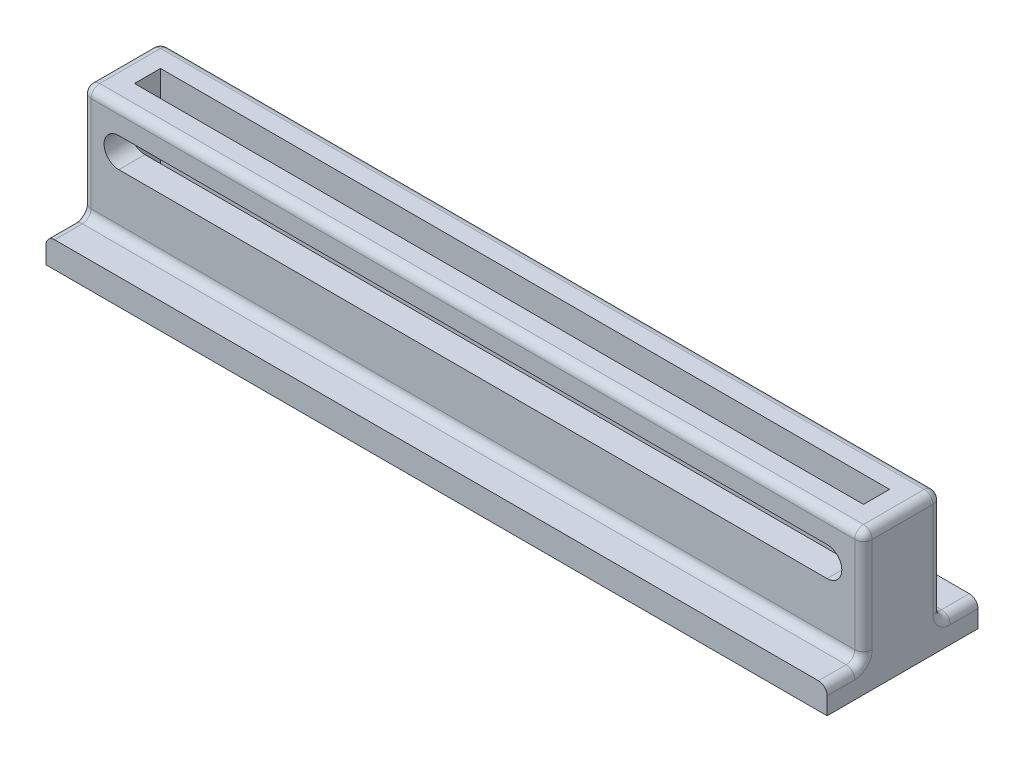
SolidWorks part; units mm, degrees
ref_plane "Front Plane" through (0, 0, 0) normal (0, 0, 1) x (1, 0, 0)
ref_plane "Top Plane" through (0, 0, 0) normal (0, 1, 0) x (1, 0, 0)
ref_plane "Right Plane" through (0, 0, 0) normal (1, 0, 0) x (0, 0, -1)
sketch "Sketch2" plane through (0, 0, 0) normal (0, 1, 0) x (1, 0, 0)
  line L1 (-45, 8.6916) -> (45, 8.6916)
  line L2 (-45, 8.6916) -> (-45, -8.6916)
  line L3 (-45, -8.6916) -> (45, -8.6916)
  line L4 (45, 8.6916) -> (45, -8.6916)
  line L5 (-45, 8.6916) -> (45, -8.6916) construction
  line L6 (-45, -8.6916) -> (45, 8.6916) construction
  point P0 (0, 0)
  dimension "D1" = 17.3831
  dimension "D2" = 90
extrude "Boss-Extrude1" add sketch "Sketch2" along normal blind 3
sketch "Sketch5" plane through (0, 3, 0) normal (0, 1, 0) x (1, 0, 0)
  line L0 (45, -8.6916) -> (45, 8.6916) construction
  line L1 (-45, 4.5) -> (45, 4.5)
  line L2 (-45, 4.5) -> (-45, -4.5)
  line L3 (-45, -4.5) -> (45, -4.5)
  line L4 (45, 4.5) -> (45, -4.5)
  line L5 (-45, 4.5) -> (45, -4.5) construction
  line L6 (-45, -4.5) -> (45, 4.5) construction
  line L7 (-42, 1.5) -> (-42, -1.5)
  line L8 (-42, -1.5) -> (42, -1.5)
  line L9 (42, 1.5) -> (42, -1.5)
  line L10 (-42, 1.5) -> (42, 1.5)
  point P0 (0, 0)
  dimension "D1" = 9
  dimension "D2" = 90
  dimension "D3" = 3
extrude "Boss-Extrude2" add sketch "Sketch5" along normal blind 13
sketch "Sketch6" plane through (0, 0, -4.5) normal (0, 0, -1) x (-1, 0, 0)
  line L0 (0, 3) -> (0, 16) construction
  line L1 (-45, 3) -> (45, 3) construction
  line L2 (-45, 16) -> (45, 16) construction
  line L4 (-42.5, 12.9) -> (42.5, 12.9)
  line L5 (-42.5, 12.9) -> (-42.5, 9.5)
  line L6 (-42.5, 9.5) -> (42.5, 9.5)
  line L7 (42.5, 12.9) -> (42.5, 9.5)
  line L8 (-42.5, 12.9) -> (42.5, 9.5) construction
  line L9 (-42.5, 9.5) -> (42.5, 12.9) construction
  point P6 (0, 11.2)
  dimension "D1" = 3.4
  dimension "D2" = 6.5
  dimension "D3" = 85
extrude "Cut-Extrude1" cut sketch "Sketch6" against normal through all
fillet "Fillet1" 2 edges at (0, 3, 1.5) (0, 3, -1.5) type full round first side face at (0, 6.25, 1.5) second side face at (0, 6.25, -1.5) middle face at (0, 3, 0)
fillet "Fillet4" 2 edges at (42.5, 12.9, 0) (42.5, 9.5, 0) type full round first side face at (0, 12.9, 0) second side face at (0, 9.5, 0) middle face at (42.5, 11.2, 0)
fillet "Fillet5" 2 edges at (-42.5, 9.5, 0) (-42.5, 12.9, 0) type full round first side face at (-0.725, 9.5, 0) second side face at (-0.725, 12.9, 0) middle face at (-42.5, 11.2, 0)
fillet "Fillet8" radius 1 14 edges at (45, 3, -6.5958) (45, 3, 6.5958) (-45, 3, -6.5958) (-45, 3, 6.5958) (0, 16, 4.5) (45, 9.5, -4.5) (45, 9.5, 4.5) (-45, 9.5, -4.5) (-45, 9.5, 4.5) (0, 3, 4.5) (0, 3, -4.5) (45, 16, 0) (-45, 16, 0) (0, 16, -4.5)
